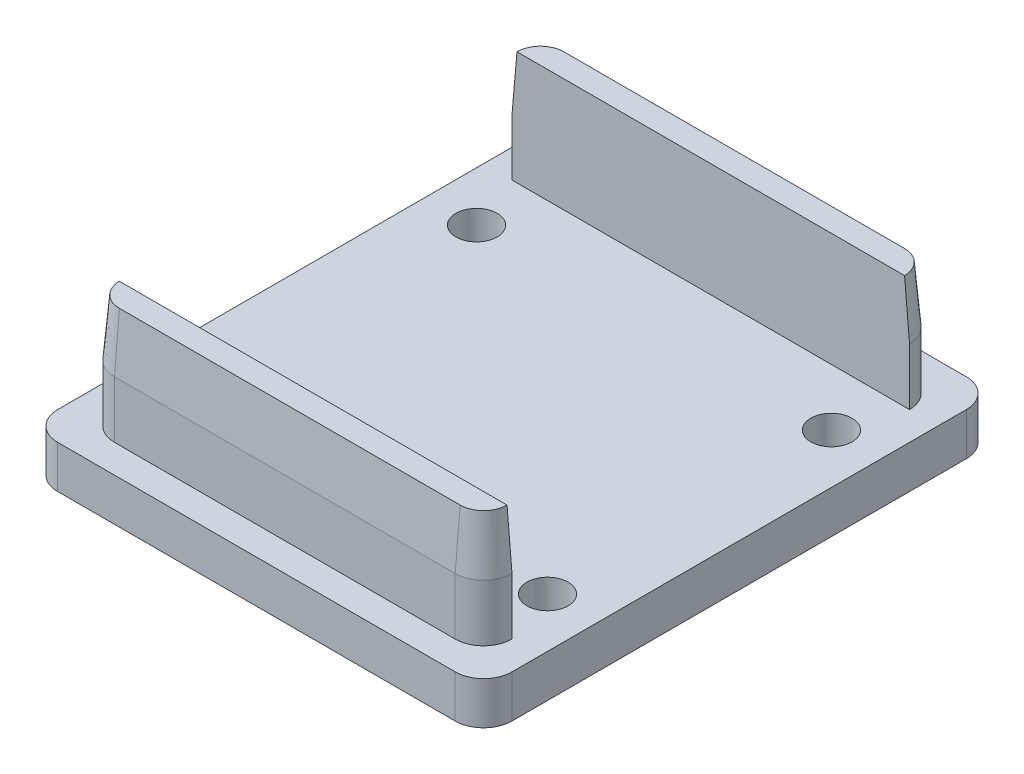
SolidWorks part; units mm, degrees
ref_plane "Front Plane" through (0, 0, 0) normal (0, 0, 1) x (1, 0, 0)
ref_plane "Top Plane" through (0, 0, 0) normal (0, 1, 0) x (1, 0, 0)
ref_plane "Right Plane" through (0, 0, 0) normal (1, 0, 0) x (0, 0, -1)
sketch "Sketch1" plane through (0, 0, 0) normal (0, 1, 0) x (1, 0, 0)
  line L1 (-16, -18) -> (16, -18)
  line L2 (-16, -18) -> (-16, 18)
  line L3 (-16, 18) -> (16, 18)
  line L4 (16, -18) -> (16, 18)
  line L5 (-16, -18) -> (16, 18) construction
  line L6 (-16, 18) -> (16, -18) construction
  point P0 (0, 0)
  dimension "D1" = 32
  dimension "D2" = 36
extrude "Boss-Extrude1" add sketch "Sketch1" along normal blind 3
sketch "Sketch4" plane through (0, 3, 0) normal (0, 1, 0) x (1, 0, 0)
  line L0 (-14, 16) -> (-14, 14)
  line L2 (-14, 14) -> (14, 14)
  line L3 (-16, 18) -> (-16, -18) construction
  line L4 (-14, -16) -> (-14, -14)
  line L5 (-14, -14) -> (14, -14)
  line L11 (-14, -16) -> (14, -16)
  line L13 (14, 16) -> (-14, 16)
  line L15 (16, 18) -> (-16, 18) construction
  line L17 (-16, -18) -> (16, -18) construction
  line L18 (14, 16) -> (14, -16) construction
  line L19 (14, 16) -> (14, 14)
  line L23 (14, -14) -> (14, -16)
  line L24 (16, -18) -> (16, 18) construction
  dimension "D1" = 2
  dimension "D2" = 2
  dimension "D3" = 2
  dimension "D4" = 2
  dimension "D5" = 2
  dimension "D6" = 2
  dimension "D7" = 2
extrude "Boss-Extrude3" add sketch "Sketch4" along normal blind 8
fillet "Fillet4" radius 2 8 edges at (14, 7, -16) (14, 7, 16) (-16, 1.5, 18) (16, 1.5, 18) (-16, 1.5, -18) (16, 1.5, -18) (-14, 7, 16) (-14, 7, -16)
chamfer "Chamfer2" distance 4 angle 5 6 edges at (13.4142, 11, 15.4142) (0, 11, 16) (13.4142, 11, -15.4142) (0, 11, -16) (-13.4142, 11, -15.4142) (-13.4142, 11, 15.4142) first distance on face at (13.2071, 7, 15.2071) first distance on face at (0, 7, 16) first distance on face at (13.2071, 7, -15.2071) first distance on face at (0, 7, -16) first distance on face at (-13.2071, 7, -15.2071) first distance on face at (-13.2071, 7, 15.2071)
sketch "Sketch5" plane through (0, 3, 0) normal (0, 1, 0) x (1, 0, 0)
  line L0 (-16, 0) -> (16, 0) construction
  line L1 (-16, 16) -> (-16, -16) construction
  line L2 (16, -16) -> (16, 16) construction
  line L3 (-13.65, 14) -> (13.65, 14) construction
  circle A0 centre (-12.5, 10) radius 1.45
  dimension "D1" = 2.9
  dimension "D2" = 4
  dimension "D3" = 3.5
extrude "Cut-Extrude1" cut sketch "Sketch5" against normal blind 2.3
mirror "Mirror1" about plane through (0, 0, 0) normal (1, 0, 0) of "Cut-Extrude1" second plane through (0, 0, 0) second plane normal (0, 0, 1)
